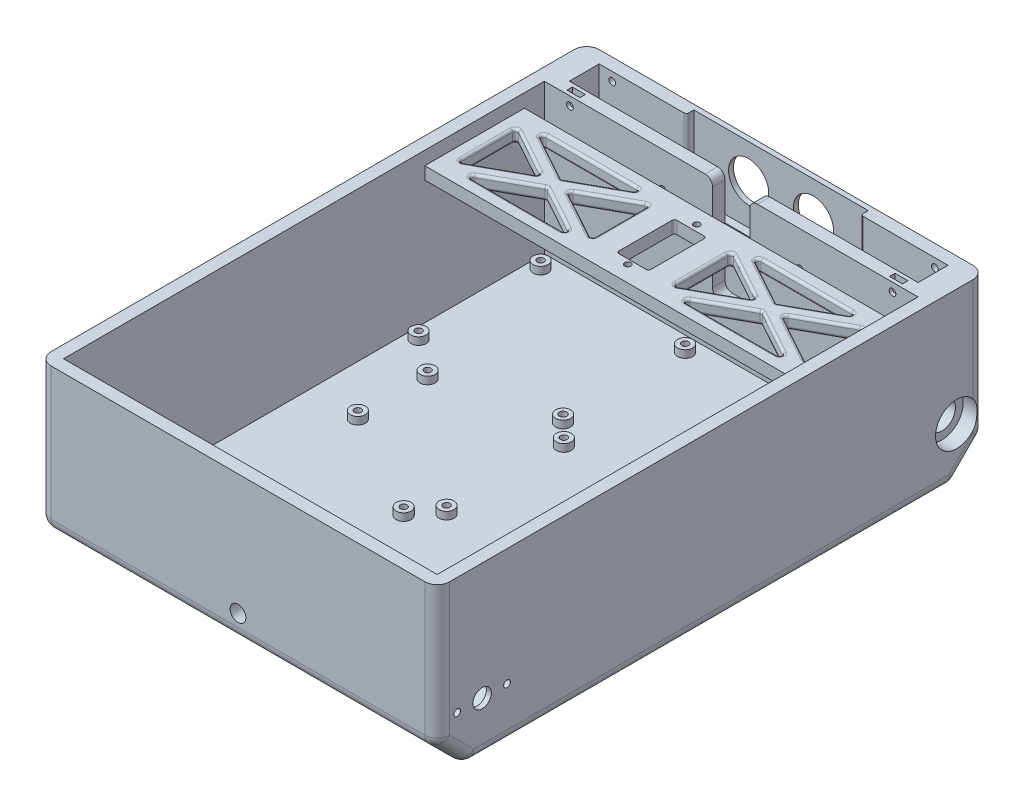
SolidWorks part; units mm, degrees
ref_plane "Front Plane" through (0, 0, 0) normal (0, 0, 1) x (1, 0, 0)
ref_plane "Top Plane" through (0, 0, 0) normal (0, 1, 0) x (1, 0, 0)
ref_plane "Right Plane" through (0, 0, 0) normal (1, 0, 0) x (0, 0, -1)
sketch "Main Body" plane through (0, 0, 0) normal (0, 1, 0) x (1, 0, 0)
  line L0 (-75, 110) -> (75, 110)
  line L1 (-75, -105) -> (75, -105)
  line L2 (-75, -105) -> (-75, 105)
  line L3 (-75, 105) -> (75, 105)
  line L4 (75, -105) -> (75, 105)
  line L5 (-75, -105) -> (75, 105) construction
  line L6 (-75, 105) -> (75, -105) construction
  line L7 (80, -105) -> (80, 105)
  line L8 (-75, -110) -> (75, -110)
  line L9 (-80, -105) -> (-80, 105)
  line L10 (-80, -110) -> (80, -110) construction
  line L11 (-80, -110) -> (-80, 110) construction
  line L12 (80, -110) -> (80, 110) construction
  line L13 (-80, 110) -> (80, 110) construction
  arc A0 (-75, -110) -> (-80, -105) centre (-75, -105) cw
  arc A1 (80, -105) -> (75, -110) centre (75, -105) cw
  arc A2 (75, 110) -> (80, 105) centre (75, 105) cw
  arc A3 (-75, 110) -> (-80, 105) centre (-75, 105) ccw
  point P0 (0, 0)
  dimension "D4" = 5
  dimension "D1" = 75
  dimension "D2" = 210
  dimension "D3" = 5
extrude "Boss-Extrude1" add sketch "Main Body" along normal blind 8 contours L1 L4 L3 L2 | L9 L8 L7 L0 L4 L1 L2 L3 region at (0, 0, -107.2797) region at (0, 0, 0)
extrude "Boss-Extrude3" add sketch "Main Body<4>" along normal blind 60 from surface starting at face at (0, 8, 0)
sketch "Main Body<4>" plane through (0, 0, 0) normal (0, 1, 0) x (1, 0, 0) same geometry as "Main Body"
sketch "Sketch1" plane through (75, 0, 0) normal (-1, 0, 0) x (0, 0, 1)
  line L0 (105, 68) -> (105, 8) construction
  line L1 (-105, 8) -> (105, 8) construction
  line L2 (79, 15.5) -> (105, 15.5)
  line L3 (79, 8) -> (105, 8)
  line L4 (79, 8) -> (79, 34)
  line L5 (79, 34) -> (105, 34)
  line L6 (105, 8) -> (105, 34)
  line L7 (79, 8) -> (105, 34) construction
  line L8 (79, 34) -> (105, 8) construction
  circle A0 centre (92, 21) radius 13
  line M2 (-105, 8) -> (105, 8)
  line M3 (105, 8) -> (105, 68)
  dimension "D1" = 26
  dimension "D2" = 7.5
extrude "Boss-Extrude4" add sketch "Sketch1" along normal up to surface (150 mm away) contours A0 L4 M2 | A0 L3 M3 region at (75, 10.5201, 82.0674) region at (75, 10.5201, 101.9326) up to face at (-75, 38, 0)
sketch "Sketch2" plane through (0, 0, 0) normal (1, 0, 0) x (0, 0, -1)
  line L0 (-105, 68) -> (-105, 15.5) construction
  line L1 (-105, 8) -> (-79, 8)
  line L2 (-105, 8) -> (-105, 15.5)
  line L3 (-105, 15.5) -> (-79, 15.5)
  line L4 (-79, 8) -> (-79, 15.5)
  line L5 (105, 8) -> (-79, 8) construction
  line L6 (-79, 8) -> (-79, 15.5) construction
  line L7 (-79, 15.5) -> (-80.2208, 15.5) construction
extrude "Cut-Extrude1" cut sketch "Sketch2" against normal mid plane 12
sketch "Sketch3" plane through (0, 8, 0) normal (0, 1, 0) x (1, 0, 0)
  line L0 (75, -105) -> (-75, -105) construction
  line L1 (-4, -79) -> (-11, -79)
  line L2 (-4, -79) -> (-4, -105)
  line L3 (-4, -105) -> (-11, -105)
  line L4 (-11, -79) -> (-11, -105)
  line L5 (0, 0) -> (0, -105) construction
  line L6 (-75, -79) -> (-6, -79) construction
  line L7 (11, -79) -> (11, -105)
  line L8 (4, -105) -> (11, -105)
  line L9 (4, -79) -> (4, -105)
  line L10 (4, -79) -> (11, -79)
  line L11 (-6, -103.7792) -> (-6, -92) construction
  dimension "D1" = 5
  dimension "D2" = 4
extrude "Boss-Extrude5" add sketch "Sketch3" along normal blind 20
sketch "Sketch4" plane through (0, 8, 0) normal (0, 1, 0) x (1, 0, 0)
  line L0 (-75, -105) -> (-75, 105) construction
  line L1 (-75, 93) -> (75, 93)
  line L2 (-75, 93) -> (-75, 88)
  line L3 (-75, 88) -> (75, 88)
  line L4 (75, 93) -> (75, 88)
  line L5 (75, 105) -> (75, -105) construction
  line L6 (-75, 105) -> (75, 105) construction
  dimension "D1" = 17
  dimension "D2" = 5
extrude "Boss-Extrude6" add sketch "Sketch4" along normal up to surface (60 mm away) up to face at (0, 68, 0)
sketch "Sketch5" plane through (80, 0, 0) normal (1, 0, 0) x (0, 0, -1)
  circle A0 centre (-92, 21) radius 3.5 construction
  circle A1 centre (-92, 21) radius 3.5
  circle A2 centre (-92, 21) radius 3.7
  dimension "D1" = 0.2
extrude "Cut-Extrude4" cut sketch "Sketch5" against normal up to next contours A1 | A2 A1 region at (80, 21, 92) region at (80, 21, 95.5953)
sketch "Sketch6" plane through (-75, 0, 0) normal (1, 0, 0) x (0, 0, -1)
  circle A0 centre (-92, 21) radius 13
  dimension "D1" = 26
extrude "Cut-Extrude5" cut sketch "Sketch6" against normal offset from surface (3 mm away) 2 up to face at (-80, 34, 0)
mirror "Mirror1" about plane through (0, 0, 0) normal (1, 0, 0) of "Cut-Extrude4"
sketch "Sketch8" plane through (75, 0, 0) normal (-1, 0, 0) x (0, 0, 1)
  circle A0 centre (92, 21) radius 13
  dimension "D1" = 26
extrude "Cut-Extrude6" cut sketch "Sketch8" against normal offset from surface (3 mm away) 2 up to face at (80, 21, 88.3)
sketch "Sketch10" plane through (80, 0, 0) normal (1, 0, 0) x (0, 0, -1)
  circle A1 centre (-82, 21) radius 1.25
  circle A2 centre (-82, 21) radius 1.25
  circle A3 centre (-102, 21) radius 1.25
  circle A4 centre (-102, 21) radius 1.25
  circle A5 centre (-92, 21) radius 12.5
  circle A6 centre (-92, 21) radius 12.5
  circle A63 centre (-102, 21) radius 1.35
  circle A64 centre (-82, 21) radius 1.35
  dimension "D4" = 2.7
extrude "Cut-Extrude7" cut sketch "Sketch10" against normal up to next contours A2 | A64 A2 | A4 | A63 A4 region at (80, 21, 82) region at (80, 21, 102) region at (80, 21, 103.3118) region at (80, 21, 83.3118)
mirror "Mirror3" about plane through (0, 0, 0) normal (1, 0, 0) of "Cut-Extrude7"
sketch "Sketch11" plane through (80, 0, 0) normal (1, 0, 0) x (0, 0, -1)
  circle A0 centre (98.55, 21.05) radius 4.45 construction
  circle A1 centre (98.55, 21.05) radius 4.45
  circle A3 centre (98.55, 21.05) radius 5.45
  dimension "D1" = 1
extrude "Cut-Extrude10" cut sketch "Sketch11" against normal through all contours A1 | A3 A1 region at (80, 21.05, -98.55) region at (80, 21.05, -93.2541)
sketch "Sketch12" plane through (-75, 0, 0) normal (1, 0, 0) x (0, 0, -1)
  line L0 (93, 8) -> (105, 8) construction
  line L1 (93, 68) -> (105, 68)
  line L2 (93, 68) -> (93, 8)
  line L3 (93, 8) -> (105, 8)
  line L4 (105, 68) -> (105, 8)
  line L6 (93, 68) -> (93, 8) construction
  line L7 (93, 68) -> (105, 68) construction
  circle A2 centre (98.55, 21.05) radius 5.45 construction
  circle A3 centre (98.55, 21.05) radius 5.45
extrude "Boss-Extrude7" add sketch "Sketch12" along normal blind 5
sketch "Sketch13" plane through (-80, 0, 0) normal (-1, 0, 0) x (0, 0, 1)
  circle A0 centre (-98.55, 21.05) radius 8.55
  circle A2 centre (-98.55, 21.05) radius 5.45 construction
  dimension "D1" = 17.1
extrude "Cut-Extrude11" cut sketch "Sketch13" against normal blind 6
mirror "Mirror4" about plane through (0, 0, 0) normal (1, 0, 0) of "Boss-Extrude7", "Cut-Extrude11"
sketch "Sketch14" plane through (0, 8, 0) normal (0, 1, 0) x (1, 0, 0)
  line L0 (-4, -105) -> (-4, -79) construction
  line L1 (-4, -95) -> (4, -95)
  line L2 (-4, -95) -> (-4, -105)
  line L3 (-4, -105) -> (4, -105)
  line L4 (4, -95) -> (4, -105)
  dimension "D1" = 10
extrude "Boss-Extrude9" add sketch "Sketch14" along normal blind 5
sketch "Sketch15" plane through (0, 0, 110) normal (0, 0, 1) x (1, 0, 0)
  arc A0 (-3, 19.5) -> (3, 19.5) centre (0, 19.5) ccw construction
  arc A1 (-3, 19.5) -> (3, 19.5) centre (0, 19.5) ccw
  arc A2 (3, 19.5) -> (-3, 19.5) centre (0, 19.5) ccw construction
  arc A3 (3, 19.5) -> (-3, 19.5) centre (0, 19.5) ccw
  arc A4 (3.15, 19.5) -> (-3.15, 19.5) centre (0, 19.5) ccw
  arc A5 (-3.15, 19.5) -> (3.15, 19.5) centre (0, 19.5) ccw
  dimension "D1" = 0.15
extrude "Cut-Extrude12" cut sketch "Sketch15" against normal up to next contours A1 A3 | A4 A5 A3 A1 region at (0, 19.5, 110) region at (0, 16.4391, 110)
sketch "Sketch16" plane through (0, 0, 0) normal (0, -1, 0) x (1, 0, 0)
  circle A0 centre (-12.5, -82) radius 1.475 construction
  circle A1 centre (-70.5, -82) radius 1.475 construction
  circle A2 centre (-70.5, -33) radius 1.475 construction
  circle A3 centre (-12.5, -33) radius 1.475 construction
  circle A4 centre (-4.2, -25) radius 1.475 construction
  circle A5 centre (-55, -21.12) radius 1.475 construction
  circle A6 centre (-55, 6.88) radius 1.475 construction
  circle A7 centre (-4.2, 22.08) radius 1.475 construction
  circle A8 centre (-12.3, 31.18) radius 1.475 construction
  circle A9 centre (24.2, 31.18) radius 1.475 construction
  circle A10 centre (37.8459, 24.117) radius 1.475 construction
  circle A11 centre (59.5541, 24.117) radius 1.475 construction
  circle A12 centre (59.5541, 68.243) radius 1.475 construction
  circle A13 centre (37.8459, 68.243) radius 1.475 construction
  circle A14 centre (24.2, 67.68) radius 1.475 construction
  circle A15 centre (-12.3, 67.68) radius 1.475 construction
  circle A16 centre (-12.5, -82) radius 1.475
  circle A17 centre (-70.5, -82) radius 1.475
  circle A18 centre (-70.5, -33) radius 1.475
  circle A19 centre (-12.5, -33) radius 1.475
  circle A20 centre (-4.2, -25) radius 1.475
  circle A21 centre (-55, -21.12) radius 1.475
  circle A22 centre (-55, 6.88) radius 1.475
  circle A23 centre (-4.2, 22.08) radius 1.475
  circle A24 centre (-12.3, 31.18) radius 1.475
  circle A25 centre (24.2, 31.18) radius 1.475
  circle A26 centre (37.8459, 24.117) radius 1.475
  circle A27 centre (59.5541, 24.117) radius 1.475
  circle A28 centre (59.5541, 68.243) radius 1.475
  circle A29 centre (37.8459, 68.243) radius 1.475
  circle A30 centre (24.2, 67.68) radius 1.475
  circle A31 centre (-12.3, 67.68) radius 1.475
  circle A32 centre (-70.5, -82) radius 1.35
  circle A33 centre (-12.5, -82) radius 1.35
  circle A34 centre (-12.5, -33) radius 1.35
  circle A35 centre (-4.2, -25) radius 1.35
  circle A36 centre (-55, -21.12) radius 1.35
  circle A37 centre (-70.5, -33) radius 1.35
  circle A38 centre (-55, 6.88) radius 1.35
  circle A39 centre (-12.3, 31.18) radius 1.35
  circle A40 centre (-4.2, 22.08) radius 1.35
  circle A41 centre (24.2, 31.18) radius 1.35
  circle A42 centre (37.8459, 24.117) radius 1.35
  circle A43 centre (59.5541, 24.117) radius 1.35
  circle A44 centre (37.8459, 68.243) radius 1.35
  circle A45 centre (59.5541, 68.243) radius 1.35
  circle A46 centre (24.2, 67.68) radius 1.35
  circle A47 centre (-12.3, 67.68) radius 1.35
  dimension "D1" = 2.7
extrude "Cut-Extrude13" cut sketch "Sketch16" against normal up to next contours A47 | A46 | A44 | A45 | A35 | A37 | A36 | A38 | A39 | A40 | A41 | A42 | A43 | A32 | A33 | A19 region at (-70.5, 0, -82) region at (-12.5, 0, -82) region at (-4.2, 0, -25) region at (-55, 0, -21.12) region at (-70.5, 0, -33) region at (-55, 0, 6.88) region at (-12.3, 0, 31.18) region at (-4.2, 0, 22.08) region at (24.2, 0, 31.18) region at (37.8459, 0, 24.117) region at (59.5541, 0, 24.117) region at (37.8459, 0, 68.243) region at (59.5541, 0, 68.243) region at (24.2, 0, 67.68) region at (-12.3, 0, 67.68)
sketch "Sketch18" plane through (75, 0, 0) normal (-1, 0, 0) x (0, 0, 1)
  line L1 (-80, 62.6) -> (-40, 62.6)
  line L2 (-80, 62.6) -> (-80, 57.6)
  line L3 (-80, 57.6) -> (-40, 57.6)
  line L4 (-40, 62.6) -> (-40, 57.6)
  line L5 (-88, 68) -> (105, 68) construction
  dimension "D1" = 5
  dimension "D2" = 30
  dimension "D3" = 40
  dimension "D4" = 5.4
extrude "Boss-Extrude11" add sketch "Sketch18" along normal up to next
sketch "Sketch19" plane through (0, 68, 0) normal (0, 1, 0) x (1, 0, 0)
  line L1 (-6.425, 71.625) -> (6.425, 71.625)
  line L2 (-6.425, 71.625) -> (-6.425, 48.375)
  line L3 (-6.425, 48.375) -> (6.425, 48.375)
  line L4 (6.425, 71.625) -> (6.425, 48.375)
  line L12 (-75, 80) -> (-75, 40)
  line L13 (-75, 40) -> (75, 40)
  line L14 (75, 40) -> (75, 80)
  line L15 (75, 80) -> (-75, 80)
  line L16 (-75, 80) -> (-75, 40)
  line L17 (-75, 40) -> (75, 40)
  line L18 (75, 40) -> (75, 80)
  line L19 (75, 80) -> (-75, 80)
  point P4 (0, 71.625)
  point P8 (0, 80)
  point P12 (6.425, 60)
  point P13 (75, 60)
  dimension "D1" = 23.25
  dimension "D2" = 12.85
  dimension "D3" = 0
extrude "Cut-Extrude14" cut sketch "Sketch19" against normal up to next contours L4 L1 L2 L3 region at (0, 68, -60)
sketch "Sketch21" plane through (0, 0, -110) normal (0, 0, -1) x (-1, 0, 0)
  circle A1 centre (-64.75, 64.5) radius 1.3
  circle A2 centre (-64.75, 64.5) radius 1.3
  circle A3 centre (64.75, 64.5) radius 1.3
  circle A4 centre (64.75, 64.5) radius 1.3
  circle A44 centre (-64.75, 64.5) radius 1.35
  circle A45 centre (64.75, 64.5) radius 1.35
  dimension "D3" = 2.7
extrude "Cut-Extrude16" cut sketch "Sketch21" against normal up to surface (22 mm away) contours A44 A2 | A2 | A45 A4 | A4 region at (64.75, 64.5, -110) region at (-64.75, 64.5, -110) region at (66.0618, 64.5, -110) region at (-63.4382, 64.5, -110) up to face at (0, 38, -88)
ref_plane "Plane1" through (0, 0, -90.5) normal (0, 0, -1) x (-1, 0, 0)
sketch "Sketch22" plane through (0, 0, -90.5) normal (0, 0, -1) x (-1, 0, 0)
  line L0 (-67.35, 66.0011) -> (-67.35, 68)
  line L1 (-62.15, 66.0011) -> (-64.75, 67.5022)
  line L2 (-64.75, 67.5022) -> (-67.35, 66.0011)
  line L3 (-67.35, 66.0011) -> (-67.35, 62.9989)
  line L4 (-67.35, 62.9989) -> (-64.75, 61.4978)
  line L5 (-64.75, 61.4978) -> (-62.15, 62.9989)
  line L6 (-62.15, 62.9989) -> (-62.15, 66.0011)
  line L7 (-67.35, 68) -> (-62.15, 68)
  line L8 (-62.15, 68) -> (-62.15, 66.0011)
  line L9 (70, 68) -> (-70, 68) construction
  line L10 (0, 0) -> (0, 68) construction
  line L11 (75, 68) -> (-75, 68) construction
  line L12 (64.75, 61.4978) -> (62.15, 62.9989)
  line L13 (67.35, 62.9989) -> (64.75, 61.4978)
  line L14 (64.75, 67.5022) -> (67.35, 66.0011)
  line L15 (67.35, 66.0011) -> (67.35, 62.9989)
  line L16 (67.35, 66.0011) -> (67.35, 68)
  line L17 (62.15, 62.9989) -> (62.15, 66.0011)
  line L18 (62.15, 68) -> (62.15, 66.0011)
  line L19 (67.35, 68) -> (62.15, 68)
  line L20 (62.15, 66.0011) -> (64.75, 67.5022)
  circle A0 centre (-64.75, 64.5) radius 2.6 construction
  circle A1 centre (-64.75, 64.5) radius 1.35 construction
  point P16 (0, 0)
  point P27 (0, 0)
  dimension "D1" = 5.2
extrude "Cut-Extrude17" cut sketch "Sketch22" against normal mid plane 2.2 contours L20 L17 L12 L13 L15 L14 | L18 L20 L14 L16 L19 | L5 L6 L1 L2 L3 L4 | L8 L7 L0 L2 L1 region at (67.2943, 67.0006, -90.5) region at (64.75, 64.5, -90.5) region at (-64.75, 64.5, -90.5) region at (-62.2057, 67.0006, -90.5)
sketch "Sketch23" plane through (0, 0, -110) normal (0, 0, -1) x (-1, 0, 0)
  circle A0 centre (64.75, 64.5) radius 2.5
  circle A1 centre (-64.75, 64.5) radius 2.5
  circle A2 centre (64.75, 64.5) radius 1.35 construction
  circle A3 centre (-64.75, 64.5) radius 1.35 construction
  point P6 (0, 0)
  point P9 (0, 0)
  dimension "D1" = 5
  dimension "D2" = 5
extrude "Cut-Extrude18" cut sketch "Sketch23" against normal mid plane 2.5
sketch "Sketch24" plane through (0, 62.6, 0) normal (0, 1, 0) x (1, 0, 0)
  circle A0 centre (0, 46.475) radius 1.2502
  arc A1 (0.4, 45.5583) -> (-0.4, 45.5583) centre (0, 46.475) ccw construction
  circle A2 centre (0, 74.175) radius 1.2502
  arc A3 (-0.4, 75.0917) -> (0, 73.1748) centre (0, 74.175) ccw construction
  point P5 (0.4, 45.5583)
  dimension "D1" = 0.25
extrude "Cut-Extrude19" cut sketch "Sketch24" against normal up to next
sketch "Sketch25" plane through (0, 62.6, 0) normal (0, 1, 0) x (1, 0, 0)
  line L1 (-11.3, 80) -> (11.3, 80)
  line L2 (-11.3, 80) -> (-11.3, 40)
  line L3 (-11.3, 40) -> (11.3, 40)
  line L4 (-75, 80) -> (-75, 40)
  line L5 (-75, 40) -> (75, 40)
  line L6 (75, 40) -> (75, 80)
  line L7 (75, 80) -> (-75, 80)
  line L8 (-75, 80) -> (-75, 40)
  line L9 (-75, 40) -> (75, 40)
  line L10 (75, 40) -> (75, 80)
  line L11 (75, 80) -> (-75, 80)
  line L12 (11.3, 80) -> (11.3, 40)
  line L13 (-11.3, 80) -> (11.3, 40) construction
  line L14 (-11.3, 40) -> (11.3, 80) construction
  line L15 (0, 80) -> (0, 40) construction
  line L16 (70, 75) -> (70, 45)
  line L17 (-70, 75) -> (-16.3, 75)
  line L18 (-70, 75) -> (-70, 45)
  line L19 (-70, 45) -> (-16.3, 45)
  line L20 (-16.3, 75) -> (-16.3, 45)
  line L21 (-70, 75) -> (-16.3, 45) construction
  line L22 (-70, 45) -> (-16.3, 75) construction
  line L23 (70, 75) -> (16.3, 45) construction
  line L24 (70, 45) -> (16.3, 75) construction
  line L25 (70, 75) -> (16.3, 75)
  line L26 (16.3, 75) -> (16.3, 45)
  line L27 (70, 45) -> (16.3, 45)
  line L28 (-75, 60) -> (-11.3, 60) construction
  line L29 (75, 60) -> (11.3, 60) construction
  line L30 (-70, 71.9362) -> (-48.3314, 60)
  line L31 (-16.3, 71.9362) -> (-37.9686, 60)
  line L32 (70, 71.9362) -> (48.3314, 60)
  line L33 (-48.3314, 60) -> (-70, 48.0638)
  line L34 (48.3314, 60) -> (70, 48.0638)
  line L35 (-65.199, 45) -> (-43.15, 57.1458)
  line L36 (65.199, 45) -> (43.15, 57.1458)
  line L37 (-43.15, 57.1458) -> (-21.101, 45)
  line L38 (43.15, 57.1458) -> (21.101, 45)
  line L39 (16.3, 71.9362) -> (37.9686, 60)
  line L40 (-37.9686, 60) -> (-16.3, 48.0638)
  line L41 (37.9686, 60) -> (16.3, 48.0638)
  line L42 (-65.199, 75) -> (-43.15, 62.8542)
  line L43 (65.199, 75) -> (43.15, 62.8542)
  line L44 (-43.15, 62.8542) -> (-21.101, 75)
  line L45 (43.15, 62.8542) -> (21.101, 75)
  line L46 (-75, 40) -> (-75, 80) construction
  line L47 (-75, 40) -> (75, 40) construction
  point P2 (0, 60)
  point P9 (-43.15, 60)
  point P10 (75, 60)
  point P24 (43.15, 60)
  point P62 (-54.1745, 68.9271)
  dimension "D2" = 150
  dimension "D3" = 5
  dimension "D4" = 5
  dimension "D5" = 5
  dimension "D6" = 26.6686
  dimension "D7" = 96.101
  dimension "D1" = 0
extrude "Cut-Extrude21" cut sketch "Sketch25" against normal up to next contours L37 L35 L19 | L33 L30 L18 | L42 L44 L17 | L31 L40 L20 | L41 L39 L26 | L45 L43 L25 | L36 L38 L27 | L32 L34 L16 region at (62.7771, 62.6, -60) region at (43.15, 62.6, -70.9514) region at (43.15, 62.6, -49.0486) region at (23.5229, 62.6, -60) region at (-43.15, 62.6, -70.9514) region at (-62.7771, 62.6, -60) region at (-23.5229, 62.6, -60) region at (-43.15, 62.6, -49.0486)
sketch "Sketch26" plane through (-80, 0, 0) normal (-1, 0, 0) x (0, 0, 1)
  line L0 (-110, 12.58) -> (-97.42, 0)
  line L1 (-110, 68) -> (-110, 0) construction
  line L2 (105, 0) -> (-105, 0) construction
  line L3 (-97.42, 0) -> (-92.42, 0)
  line L4 (-92.42, 0) -> (-110, 17.58)
  line L5 (-110, 17.58) -> (-110, 12.58)
  line L6 (-110, 12.58) -> (-110, 0)
  line L7 (-110, 0) -> (-97.42, 0)
  circle A1 centre (-98.55, 21.05) radius 8.55 construction
  line M5 (-105, 15.4375) -> (-105, 0)
  line M6 (-105, 0) -> (105, 0)
  dimension "D1" = 2
  dimension "D2" = 5
  dimension "D3" = 45
extrude "Cut-Extrude22" cut sketch "Sketch26" against normal up to next contours L6 L7 L0 M5 | L0 M5 M6 region at (-80, 5.1434, -107.7067) region at (-80, 2.5267, -102.4733)
mirror "Mirror5" about plane through (0, 0, 0) normal (0, 0, 1) of "Cut-Extrude22"
fillet "Fillet1" radius 5 14 edges at (80, 3.79, -101.21) (78.5355, 11.1156, -108.5355) (-80, 3.79, -101.21) (-78.5355, 11.1156, -108.5355) (80, 3.79, 101.21) (78.5355, 11.1156, 108.5355) (-80, 3.79, 101.21) (-78.5355, 11.1156, 108.5355) (0, 0, -97.42) (0, 12.58, -110) (0, 0, 97.42) (0, 12.58, 110) (-80, 0, 0) (80, 0, 0)
fillet "Fillet2" radius 1 76 edges at (-32.1255, 57.6, -51.0729) (-32.1255, 62.6, -51.0729) (-21.101, 60.1, -45) (-43.15, 62.6, -45) (-43.15, 57.6, -45) (-54.1745, 57.6, -51.0729) (-65.199, 60.1, -45) (-54.1745, 62.6, -51.0729) (-43.15, 60.1, -57.1458) (32.1255, 57.6, -68.9271) (32.1255, 62.6, -68.9271) (21.101, 60.1, -75) (43.15, 62.6, -75) (43.15, 57.6, -75) (54.1745, 57.6, -68.9271) (65.199, 60.1, -75) (54.1745, 62.6, -68.9271) (43.15, 60.1, -62.8542) (54.1745, 62.6, -51.0729) (54.1745, 57.6, -51.0729) (43.15, 57.6, -45) (65.199, 60.1, -45) (43.15, 62.6, -45) (21.101, 60.1, -45) (32.1255, 62.6, -51.0729) (43.15, 60.1, -57.1458) (32.1255, 57.6, -51.0729) (59.1657, 62.6, -65.9681) (59.1657, 57.6, -65.9681) (70, 57.6, -60) (70, 60.1, -71.9362) (70, 62.6, -60) (70, 60.1, -48.0638) (59.1657, 62.6, -54.0319) (48.3314, 60.1, -60) (59.1657, 57.6, -54.0319) (-54.1745, 62.6, -68.9271) (-54.1745, 57.6, -68.9271) (-43.15, 57.6, -75) (-65.199, 60.1, -75) (-43.15, 62.6, -75) (-21.101, 60.1, -75) (-32.1255, 62.6, -68.9271) (-43.15, 60.1, -62.8542) (-32.1255, 57.6, -68.9271) (-59.1657, 57.6, -54.0319) (-59.1657, 62.6, -54.0319) (-70, 60.1, -48.0638) (-70, 62.6, -60) (-70, 57.6, -60) (-59.1657, 57.6, -65.9681) (-70, 60.1, -71.9362) (-59.1657, 62.6, -65.9681) (-48.3314, 60.1, -60) (-27.1343, 62.6, -65.9681) (-27.1343, 57.6, -65.9681) (-16.3, 57.6, -60) (-16.3, 60.1, -71.9362) (-16.3, 62.6, -60) (-16.3, 60.1, -48.0638) (-27.1343, 62.6, -54.0319) (-37.9686, 60.1, -60) (-27.1343, 57.6, -54.0319) (27.1343, 57.6, -54.0319) (27.1343, 62.6, -54.0319) (16.3, 60.1, -48.0638) (16.3, 62.6, -60) (16.3, 57.6, -60) (27.1343, 57.6, -65.9681) (16.3, 60.1, -71.9362) (27.1343, 62.6, -65.9681) (37.9686, 60.1, -60) (6.425, 60.1, -48.375) (-6.425, 60.1, -48.375) (-6.425, 60.1, -71.625) (6.425, 60.1, -71.625)
sketch "Sketch33" plane through (0, 0, -110) normal (0, 0, -1) x (-1, 0, 0)
  circle A0 centre (-13, 53.9999) radius 8.075
  circle A1 centre (13, 53.9999) radius 8.075
  circle A2 centre (-13, 53.9999) radius 7.3 construction
  circle A3 centre (13, 53.9999) radius 7.3 construction
  dimension "D1" = 16.15
extrude "Cut-Extrude27" cut sketch "Sketch33" against normal up to next
sketch "Sketch34" plane through (0, 0, -93) normal (0, 0, -1) x (-1, 0, 0)
  circle A0 centre (27.525, 54) radius 1.35 construction
  circle A1 centre (27.525, 54) radius 1.35
  circle A2 centre (-27.525, 54) radius 1.35 construction
  circle A3 centre (-27.525, 54) radius 1.35
  circle A4 centre (-27.525, 54) radius 1.35
  circle A5 centre (27.525, 54) radius 1.35
  dimension "D1" = 2.7
  dimension "D2" = 2.7
extrude "Cut-Extrude28" cut sketch "Sketch34" against normal up to next contours A3 | A1 region at (-27.525, 54, -93) region at (27.525, 54, -93)
sketch "Sketch35" plane through (0, 68, 0) normal (0, 1, 0) x (1, 0, 0)
  line L0 (70, 93) -> (-70, 93) construction
  line L1 (-7.5, 93) -> (7.5, 93)
  line L2 (-7.5, 93) -> (-7.5, 88)
  line L3 (-7.5, 88) -> (7.5, 88)
  line L4 (7.5, 93) -> (7.5, 88)
  line L5 (-7.5, 93) -> (7.5, 88) construction
  line L6 (-7.5, 88) -> (7.5, 93) construction
  line L7 (-75, 88) -> (75, 88) construction
  point P0 (0, 90.5)
  dimension "D1" = 15
extrude "Cut-Extrude29" cut sketch "Sketch35" against normal offset from surface (41 mm away) 19 up to face at (-4.2, 8, -23.65)
fillet "Fillet4" radius 3 9 edges at (0, 8, 95) (-7.5, 28, 79) (-7.5, 28, 105) (7.5, 28, 105) (7.5, 28, 79) (-7.5, 68, -90.5) (7.5, 68, -90.5) (-7.5, 27, -90.5) (7.5, 27, -90.5)
fillet "Fillet5" radius 1 1 edges at (0, 13, 95)
sketch "Sketch36" plane through (0, 68, 0) normal (0, 1, 0) x (1, 0, 0)
  line L0 (-70, 105) -> (70, 105) construction
  line L1 (-35, 108) -> (35, 108)
  line L2 (-35, 108) -> (-35, 105)
  line L3 (-35, 105) -> (35, 105)
  line L4 (35, 108) -> (35, 105)
  line L5 (-75, 110) -> (75, 110) construction
  point P6 (0, 108)
  dimension "D1" = 70
  dimension "D2" = 2
extrude "Cut-Extrude30" cut sketch "Sketch36" against normal blind 30
fillet "Fillet6" radius 1 2 edges at (35, 53, -105) (-35, 53, -105)
sketch "Sketch37" plane through (0, 8, 0) normal (0, 1, 0) x (1, 0, 0)
  line L8 (-4, -79) -> (-4, -92)
  line L9 (-4, -92) -> (4, -92)
  line L10 (4, -92) -> (4, -79)
  line L11 (4, -79) -> (75, -79)
  line L12 (75, -79) -> (75, 88)
  line L13 (75, 88) -> (-75, 88)
  line L14 (-75, 88) -> (-75, -79)
  line L15 (-75, -79) -> (-4, -79)
  line L16 (-4, -79) -> (-4, -92)
  line L17 (-4, -92) -> (4, -92)
  line L18 (4, -92) -> (4, -79)
  line L19 (4, -79) -> (75, -79)
  line L20 (75, -79) -> (75, 88)
  line L21 (75, 88) -> (-75, 88)
  line L22 (-75, 88) -> (-75, -79)
  line L23 (-75, -79) -> (-4, -79)
  circle A0 centre (-12.5, 82) radius 1.35 construction
  circle A1 centre (-4.2, 25) radius 1.35 construction
  circle A2 centre (-12.5, 33) radius 1.475 construction
  circle A3 centre (-70.5, 33) radius 1.35 construction
  circle A4 centre (-55, 21.12) radius 1.35 construction
  circle A5 centre (-55, -6.88) radius 1.35 construction
  circle A6 centre (-12.3, -31.18) radius 1.35 construction
  circle A7 centre (-4.2, -22.08) radius 1.35 construction
  circle A8 centre (24.2, -31.18) radius 1.35 construction
  circle A9 centre (37.8459, -24.117) radius 1.35 construction
  circle A10 centre (59.5541, -24.117) radius 1.35 construction
  circle A11 centre (59.5541, -68.243) radius 1.35 construction
  circle A12 centre (37.8459, -68.243) radius 1.35 construction
  circle A13 centre (24.2, -67.68) radius 1.35 construction
  circle A14 centre (-12.3, -67.68) radius 1.35 construction
  circle A15 centre (-70.5, 82) radius 1.35 construction
  circle A16 centre (-12.5, 82) radius 1.35
  circle A17 centre (-4.2, 25) radius 1.35
  circle A18 centre (-12.5, 33) radius 1.475
  circle A19 centre (-70.5, 33) radius 1.35
  circle A20 centre (-55, 21.12) radius 1.35
  circle A21 centre (-55, -6.88) radius 1.35
  circle A22 centre (-12.3, -31.18) radius 1.35
  circle A23 centre (-4.2, -22.08) radius 1.35
  circle A24 centre (24.2, -31.18) radius 1.35
  circle A25 centre (37.8459, -24.117) radius 1.35
  circle A26 centre (59.5541, -24.117) radius 1.35
  circle A27 centre (59.5541, -68.243) radius 1.35
  circle A28 centre (37.8459, -68.243) radius 1.35
  circle A29 centre (24.2, -67.68) radius 1.35
  circle A30 centre (-12.3, -67.68) radius 1.35
  circle A31 centre (-70.5, 82) radius 1.35
  circle A32 centre (-12.3, -67.68) radius 3
  circle A33 centre (24.2, -67.68) radius 3
  circle A34 centre (37.8459, -68.243) radius 3
  circle A35 centre (59.5541, -68.243) radius 3
  circle A36 centre (24.2, -31.18) radius 3
  circle A37 centre (37.8459, -24.117) radius 3
  circle A38 centre (59.5541, -24.117) radius 3
  circle A39 centre (-4.2, -22.08) radius 3
  circle A40 centre (-12.3, -31.18) radius 3
  circle A41 centre (-4.2, 25) radius 3
  circle A42 centre (-55, -6.88) radius 3
  circle A43 centre (-55, 21.12) radius 3
  circle A44 centre (-12.5, 33) radius 3
  circle A45 centre (-12.5, 82) radius 3
  circle A46 centre (-70.5, 82) radius 3
  circle A47 centre (-70.5, 33) radius 3
  circle M9 centre (-4.2, 25) radius 1.35
  circle M10 centre (59.5541, -68.243) radius 1.35
  circle M11 centre (37.8459, -68.243) radius 1.35
  circle M12 centre (24.2, -67.68) radius 1.35
  circle M13 centre (-70.5, 33) radius 1.35
  circle M14 centre (-55, 21.12) radius 1.35
  circle M15 centre (-55, -6.88) radius 1.35
  circle M16 centre (-12.3, -31.18) radius 1.35
  circle M17 centre (-4.2, -22.08) radius 1.35
  circle M18 centre (24.2, -31.18) radius 1.35
  circle M19 centre (37.8459, -24.117) radius 1.35
  circle M20 centre (59.5541, -24.117) radius 1.35
  circle M21 centre (-70.5, 82) radius 1.35
  circle M22 centre (-12.5, 82) radius 1.35
  circle M23 centre (-12.5, 33) radius 1.475
  circle M24 centre (-12.3, -67.68) radius 1.35
  dimension "D2" = 6
  dimension "D1" = 0
extrude "Boss-Extrude12" add sketch "Sketch37" along normal blind 3 contours A46 M21 | A45 M22 | A44 M23 | A41 M9 | A47 M13 | A43 M14 | A42 M15 | A38 M20 | A35 M10 | A34 M11 | A37 M19 | A36 M18 | A33 M12 | A39 M17 | A40 M16 | A32 M24 region at (-15.2151, 8, 67.68) region at (21.2849, 8, 67.68) region at (34.9307, 8, 68.243) region at (56.639, 8, 68.243) region at (21.2849, 8, 31.18) region at (34.9307, 8, 24.117) region at (56.639, 8, 24.117) region at (-7.1151, 8, 22.08) region at (-15.2151, 8, 31.18) region at (-7.1151, 8, -25) region at (-57.9151, 8, 6.88) region at (-57.9151, 8, -21.12) region at (-15.4151, 8, -33) region at (-15.4151, 8, -82) region at (-73.4151, 8, -82) region at (-73.4151, 8, -33)
equation "\"Screw\"= 2.7"
equation "\"D1@Sketch16\"=\"Screw\""
equation "\"D4@Sketch10\"=\"Screw\""
equation "\"D3@Sketch21\"=\"Screw\""
equation "\"D2@Sketch34\"=\"Screw\""
equation "\"D1@Sketch34\"=\"Screw\""
